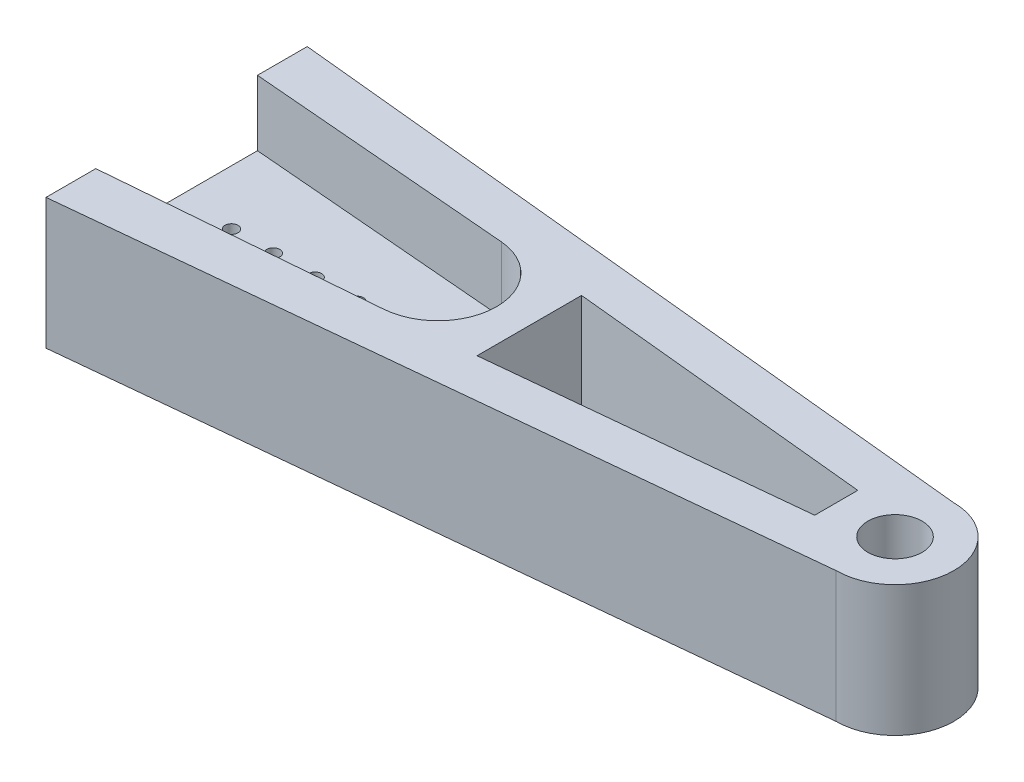
SolidWorks part; units mm, degrees
ref_plane "Front Plane" through (0, 0, 0) normal (0, 0, 1) x (1, 0, 0)
ref_plane "Top Plane" through (0, 0, 0) normal (0, 1, 0) x (1, 0, 0)
ref_plane "Right Plane" through (0, 0, 0) normal (1, 0, 0) x (0, 0, -1)
sketch "Sketch1" plane through (0, 0, 0) normal (0, 1, 0) x (1, 0, 0)
  line L0 (0.5417, 6.4774) -> (30.3333, 3.9861) construction
  line L5 (0.5417, -6.4774) -> (30.3333, -3.9861) construction
  line L6 (10, 5.6864) -> (30.3333, 3.9861) construction
  line L8 (10, 10) -> (10, 6.1882)
  line L11 (10, -5.6864) -> (30.3333, -3.9861) construction
  line L13 (10, 6.1882) -> (30.375, 4.4843)
  line L15 (10, -6.1882) -> (30.375, -4.4843)
  line L16 (9.5, 6.23) -> (30.375, 4.4843) construction
  line L17 (9.5, 6.23) -> (9.5, -6.23) construction
  line L18 (9.5, -6.23) -> (30.375, -4.4843) construction
  line L19 (10, 5.6864) -> (10, -5.6864) construction
  line L20 (10, -6.1882) -> (10, -10)
  line L21 (10, 6.1882) -> (10, 10)
  line L22 (10, -6.1882) -> (10, -10)
  line L23 (10, 10) -> (65, 4.5)
  line L24 (10, -10) -> (65, -4.5)
  arc A0 (0.5417, 6.4774) -> (0.5417, -6.4774) centre (0, 0) ccw construction
  arc A1 (30.3333, -3.9861) -> (30.3333, 3.9861) centre (30, 0) ccw construction
  circle A2 centre (30.5, 0) radius 0.5 construction
  circle A3 centre (27.3, 0) radius 0.5 construction
  circle A4 centre (24.1, 0) radius 0.5 construction
  circle A5 centre (20.9, 0) radius 0.5 construction
  circle A6 centre (17.7, 0) radius 0.5 construction
  circle A7 centre (14.5, 0) radius 0.5 construction
  circle A8 centre (0, 0) radius 2.7 construction
  arc A9 (30.3333, 3.9861) -> (30.3333, -3.9861) centre (30, 0) cw construction
  arc A10 (30.375, 4.4843) -> (30.375, -4.4843) centre (30, 0) cw
  circle A11 centre (65, 0) radius 2.075
  arc A12 (65, 4.5) -> (65, -4.5) centre (65, 0) cw
  dimension "D1" = 13
  dimension "D2" = 8
  dimension "D5" = 1
  dimension "D11" = 5.4
  dimension "D17" = 4.15
  dimension "D3" = 30
  dimension "D4" = 30.5
  dimension "D6" = 14.5
  dimension "D7" = 17.7
  dimension "D8" = 20.9
  dimension "D9" = 24.1
  dimension "D10" = 27.3
  dimension "D12" = 10
  dimension "D14" = 20
  dimension "D16" = 65
  dimension "D18" = 55
  dimension "D19" = 55
  dimension "D20" = 5.5
  dimension "D21" = 5.5
  dimension "D13" = 0.5
extrude "Boss-Extrude1" add sketch "Sketch1" along normal blind 5 contours L13 A10 L15 L20 L8 A11 region at (40.7046, 0, 0)
sketch "Sketch3" plane through (0, 0, 0) normal (0, 1, 0) x (1, 0, 0)
  line L0 (60.5, -1.65) -> (60.5, 1.65)
  line L2 (37, 4) -> (37, -4)
  line L3 (37, -4) -> (60.5, -1.65)
  line L5 (60.5, 1.65) -> (37, 4)
  line L6 (10, 10) -> (10, 6.1882) construction
  line L7 (10, 10) -> (65, 4.5) construction
  line L8 (10, -10) -> (65, -4.5) construction
  circle A0 centre (65, 0) radius 2.075 construction
  point P3 (56.4399, 2.5539)
  point P6 (37, 0)
  point P8 (57.0193, -1.3986)
  point P13 (54.2335, 3.2767)
  point P15 (52.4537, 3.4546)
  point P16 (55.0816, 3.1918)
  dimension "D2" = 4.5
  dimension "D1" = 8
  dimension "D3" = 27
sketch "Sketch4" plane through (0, 0, 0) normal (0, 1, 0) x (1, 0, 0)
  line L0 (10, 10) -> (10, -10)
  line L2 (10, 10) -> (65, 4.5)
  line L5 (10, -10) -> (65, -4.5)
  circle A0 centre (14.2, 0) radius 0.5
  arc A1 (65, 4.5) -> (65, -4.5) centre (65, 0) cw
  circle A2 centre (17.4, 0) radius 0.5
  circle A3 centre (20.6, 0) radius 0.5
  circle A4 centre (23.8, 0) radius 0.5
  circle A5 centre (27, 0) radius 0.5
  circle A6 centre (30.2, 0) radius 0.5
  circle A7 centre (65, 0) radius 2.1
  dimension "D2" = 1
  dimension "D4" = 3.2
  dimension "D5" = 4.2
  dimension "D1" = 4.2
  dimension "D3" = 6
extrude "Boss-Extrude4" add sketch "Sketch4" against normal blind 5
extrude "Cut-Extrude1" cut sketch "Sketch3" along normal blind 5 and the other way blind 5
